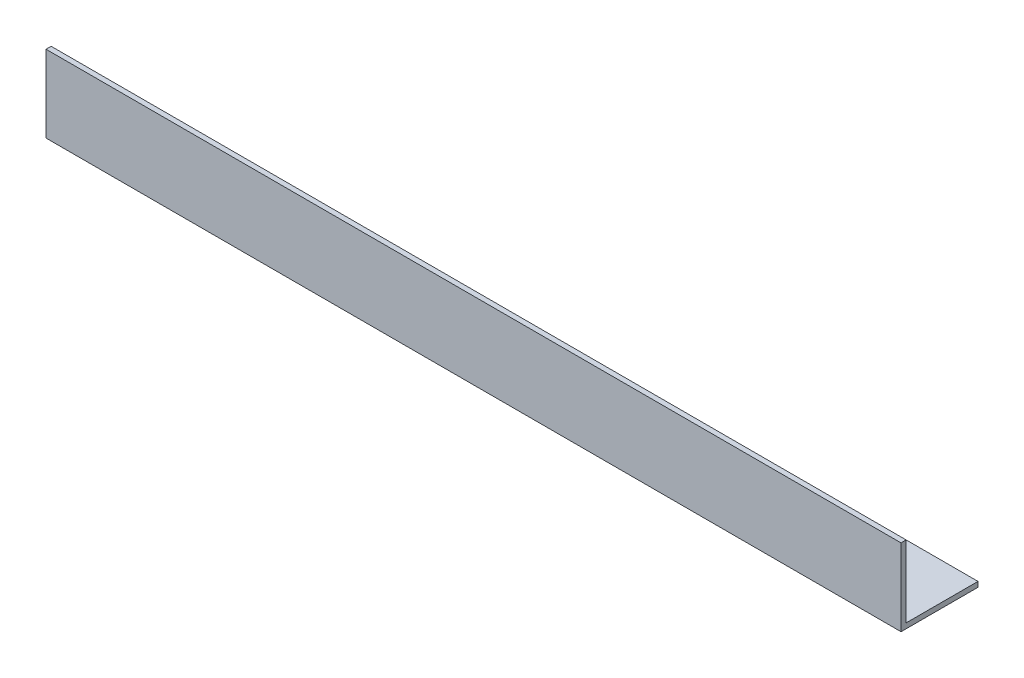
SolidWorks part; units mm, degrees
ref_plane "Спереди" through (0, 0, 0) normal (0, 0, 1) x (1, 0, 0)
ref_plane "Сверху" through (0, 0, 0) normal (0, 1, 0) x (1, 0, 0)
ref_plane "Справа" through (0, 0, 0) normal (1, 0, 0) x (0, 0, -1)
sketch "Эскиз1" plane through (0, 0, 0) normal (1, 0, 0) x (0, 0, -1)
  line L0 (0, 0) -> (0, 45)
  line L1 (0, 0) -> (45, 0)
extrude "Вытянуть-Тонкостенный1" add sketch "Эскиз1" along normal blind 500 thin thin type one direction reverse wall 3
